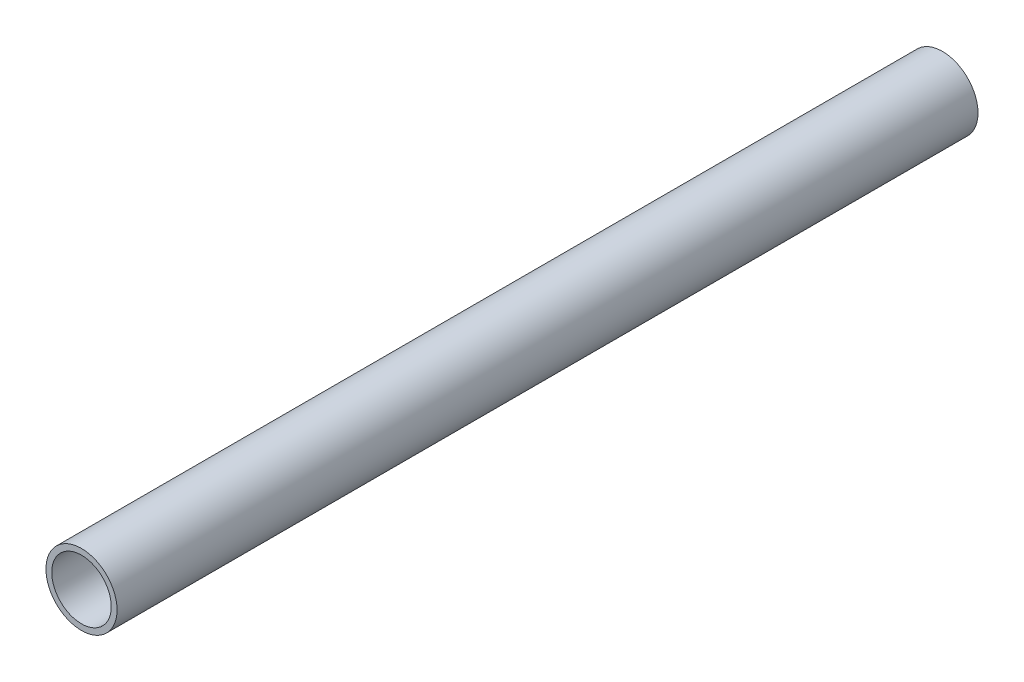
SolidWorks part; units mm, degrees
material "PVC Rigid"
ref_plane "Front Plane" through (0, 0, 0) normal (0, 0, 1) x (1, 0, 0)
ref_plane "Top Plane" through (0, 0, 0) normal (0, 1, 0) x (1, 0, 0)
ref_plane "Right Plane" through (0, 0, 0) normal (1, 0, 0) x (0, 0, -1)
sketch "Sketch1" plane through (0, 0, 0) normal (0, 0, 1) x (1, 0, 0)
  circle A0 centre (0, 0) radius 20.193
  circle A1 centre (0, 0) radius 24.13
  dimension "D1" = 48.26
  dimension "D2" = 40.386
extrude "Boss-Extrude1" add sketch "Sketch1" along normal blind 584.2
ref_axis "Axis1" through (0, 0, 628.6881) along (0, 0, -1)
